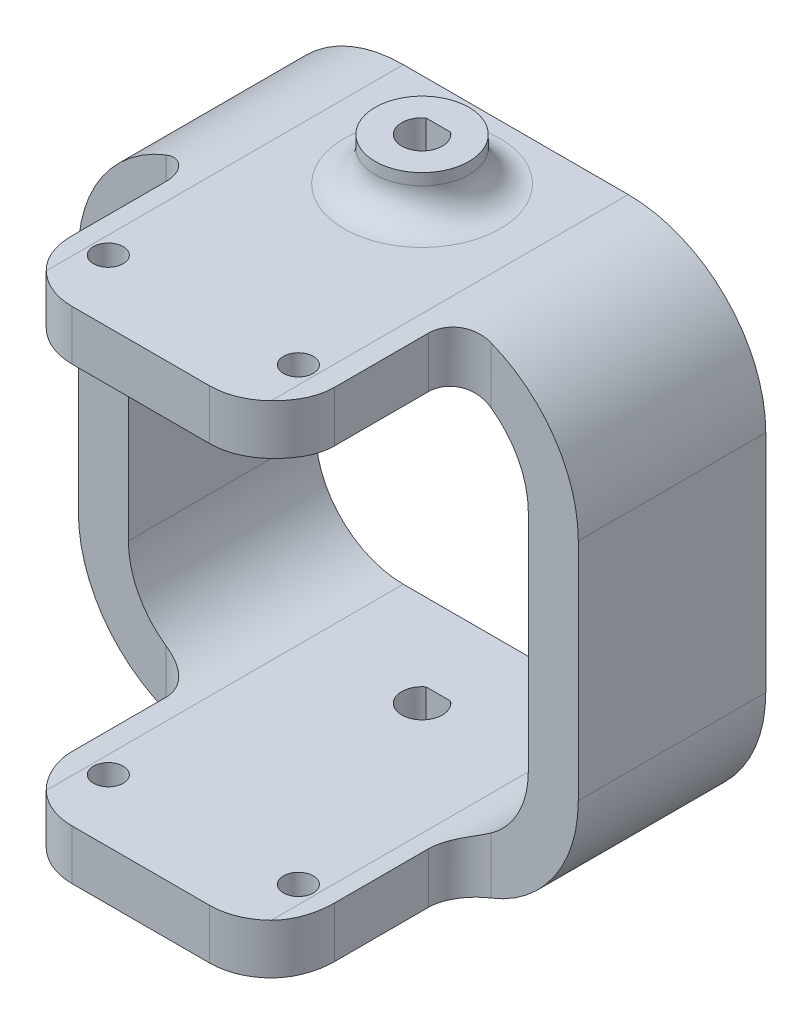
SolidWorks part; units mm, degrees
material "Plastique personnalisé"
ref_plane "Plan de face" through (0, 0, 0) normal (0, 0, 1) x (1, 0, 0)
ref_plane "Plan de dessus" through (0, 0, 0) normal (0, 1, 0) x (1, 0, 0)
ref_plane "Plan de droite" through (0, 0, 0) normal (1, 0, 0) x (0, 0, -1)
sketch "Esquisse1" plane through (0, 0, 0) normal (0, 0, 1) x (1, 0, 0)
  line L1 (40, -40) -> (-40, -40)
  line L2 (40, -40) -> (40, 40)
  line L3 (40, 40) -> (-40, 40)
  line L4 (-40, -40) -> (-40, 40)
  line L5 (40, -40) -> (-40, 40) construction
  line L6 (40, 40) -> (-40, -40) construction
  line L7 (-32, -32) -> (32, -32)
  line L8 (-32, -32) -> (-32, 32)
  line L9 (-32, 32) -> (32, 32)
  line L10 (32, -32) -> (32, 32)
  line L11 (-32, -32) -> (32, 32) construction
  line L12 (-32, 32) -> (32, -32) construction
  point P0 (0, 0)
  point P11 (0, 0)
  dimension "D1" = 8
  dimension "D3" = 80
extrude "Boss.-Extru.1" add sketch "Esquisse1" along normal mid plane 30
sketch "Esquisse2" plane through (0, 0, 0) normal (1, 0, 0) x (0, 0, -1)
  circle A0 centre (0, 0) radius 5
  dimension "D1" = 10
extrude "Enlèv. mat.-Extru.1" [suppressed] cut sketch "Esquisse2" against normal through all both and the other way through all
sketch "Esquisse3" plane through (0, -40, 0) normal (0, -1, 0) x (-1, 0, 0)
  circle A0 centre (0, 0) radius 5
  dimension "D1" = 10
extrude "Boss.-Extru.2" [suppressed] add sketch "Esquisse3" along normal blind 20
mirror "Symétrie1" [suppressed] about plane through (0, 0, 0) normal (0, 1, 0)
sketch "Esquisse7" plane through (0, 0, 15) normal (0, 0, 1) x (1, 0, 0)
  line L0 (40, 40) -> (-40, 40) construction
  line L1 (21, 32) -> (-21, 32)
  line L2 (21, 32) -> (21, 40)
  line L3 (21, 40) -> (-21, 40)
  line L4 (-21, 32) -> (-21, 40)
  line L5 (40, 40) -> (-40, 40) construction
  line L6 (32, 32) -> (-32, 32) construction
  point P10 (0, 40)
  point P11 (0, 40)
  dimension "D1" = 42
extrude "Boss.-Extru.4" add sketch "Esquisse7" along normal blind 30
sketch "Esquisse5" [suppressed] plane through (0, -60, 0) normal (0, -1, 0) x (1, 0, 0)
  circle A0 centre (0, 0) radius 3
  circle A1 centre (0, 0) radius 5 construction
  dimension "D1" = 6
extrude "Boss.-Extru.3" [suppressed] add sketch "Esquisse5" along normal blind 15
sketch "Esquisse6" [suppressed] plane through (0, -75, 0) normal (0, -1, 0) x (1, 0, 0)
  line L1 (3, -3) -> (-3, -3)
  line L2 (3, -3) -> (3, -1.8)
  line L3 (3, -1.8) -> (-3, -1.8)
  line L4 (-3, -3) -> (-3, -1.8)
  circle A0 centre (0, 0) radius 3 construction
  dimension "D1" = 1.2
extrude "Enlèv. mat.-Extru.2" [suppressed] cut sketch "Esquisse6" against normal up to surface (15 mm away) contours L1 L4 L3 L2 up to face at (0, -40, 0)
sketch "Esquisse12" plane through (0, 40, 0) normal (0, 1, 0) x (1, 0, 0)
  circle A0 centre (0, 0) radius 7.5
  dimension "D1" = 15
extrude "Boss.-Extru.5" add sketch "Esquisse12" along normal blind 6.84
hole_wizard "Perçage pour écrous auto-bloquants 300® #6 (SP)1" positions "Esquisse10" profile "Esquisse9" hole size "#6-32" standard "PEM® Inch" end condition through all
sketch "Esquisse10" plane through (0, 40, 0) normal (0, -1, 0) x (0, 0, -1)
  line L0 (-35, 15.205) -> (-35, -15.205) construction
  line L3 (-35, 0) -> (-45, 0) construction
  line L6 (-45, 21) -> (-45, -21) construction
  point P0 (-35, 15.205)
  point P2 (-35, -15.205)
  point P20 (-45, 0)
  dimension "D1" = 30.41
  dimension "D2" = 10
sketch "Esquisse9" plane through (15.205, 40, 35) normal (1, 0, 0) x (0, 0, 1)
  line L0 (0, 0) -> (0, 80)
  line L1 (0, 80) -> (2.3812, 80)
  line L2 (2.3812, 80) -> (2.3812, 0)
  line L5 (2.3812, 0) -> (0, 0)
  line L11 (0, -6.35) -> (0, 107.95) construction
  dimension "Diamètre du perçage jusqu'au prochain" = 4.7625
  dimension "Profondeur du perçage jusqu'au prochain" = 80
fillet "Congé1" radius 10 2 edges at (21, 36, 45) (-21, 36, 45)
mirror "Symétrie2" about plane through (0, 0, 0) normal (0, 1, 0) of "Boss.-Extru.5", "Congé1", "Perçage pour écrous auto-bloquants 300® #6 (SP)1", "Boss.-Extru.4"
fillet "Congé2" radius 22 4 edges at (40, -40, 0) (-40, -40, 0) (-40, 40, 0) (40, 40, 0)
fillet "Congé3" radius 14 4 edges at (-32, 32, 0) (-32, -32, 0) (32, -32, 0) (32, 32, 0)
fillet "Congé4" radius 5 6 edges at (-21, -35.7346, 15) (-21, 35.7346, 15) (21, -35.7346, 15) (21, 35.7346, 15) (0, -40, 7.5) (0, 40, -7.5)
sketch "Esquisse11" plane through (0, -46.84, -40) normal (0, 1, 0) x (1, 0, 0)
  line L0 (40, -40) -> (-40, -40) construction
  line L1 (40, -25) -> (40, -55) construction
  line L2 (-40, -55) -> (-40, -25) construction
  line L3 (1.9649, -37.405) -> (-1.9649, -37.405)
  arc A0 (-1.9649, -37.405) -> (1.9649, -37.405) centre (0, -40) ccw
  dimension "D1" = 6.51
  dimension "D2" = 5.85
extrude "Enlèv. mat.-Extru.3" cut sketch "Esquisse11" along normal through all
